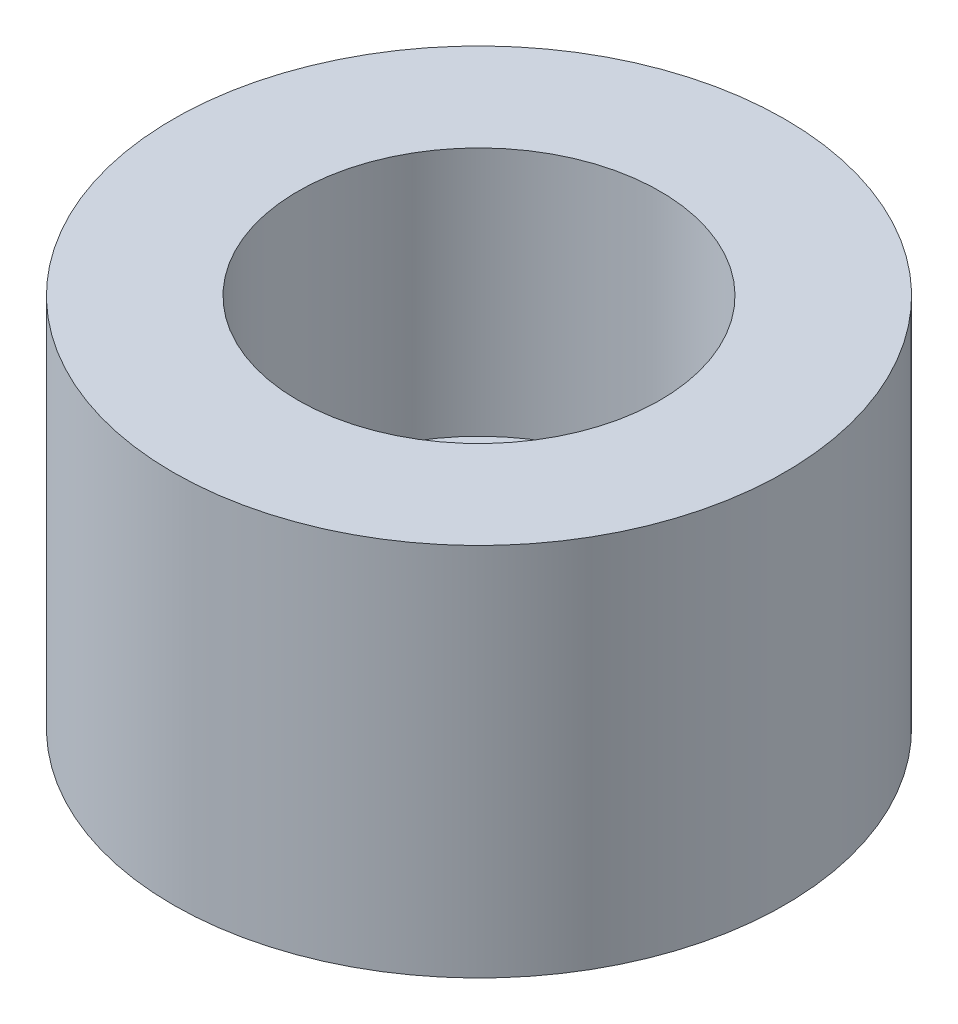
SolidWorks part; units mm, degrees
ref_plane "Front Plane" through (0, 0, 0) normal (0, 0, 1) x (1, 0, 0)
ref_plane "Top Plane" through (0, 0, 0) normal (0, 1, 0) x (1, 0, 0)
ref_plane "Right Plane" through (0, 0, 0) normal (1, 0, 0) x (0, 0, -1)
sketch "Sketch1" plane through (0, 0, 0) normal (0, 1, 0) x (1, 0, 0)
  circle A0 centre (0, 0) radius 2.9
  circle A1 centre (0, 0) radius 4.9
  dimension "D1" = 5.8
  dimension "D2" = 2
extrude "Boss-Extrude1" add sketch "Sketch1" along normal blind 4
extrude "Boss-Extrude2" add sketch "Sketch1<2>" against normal blind 2 contours A0 | A1 A0 region at (0, 0, 0) region at (-4.7614, 0, 0)
sketch "Sketch1<2>" plane through (0, 0, 0) normal (0, 1, 0) x (1, 0, 0) same geometry as "Sketch1"
